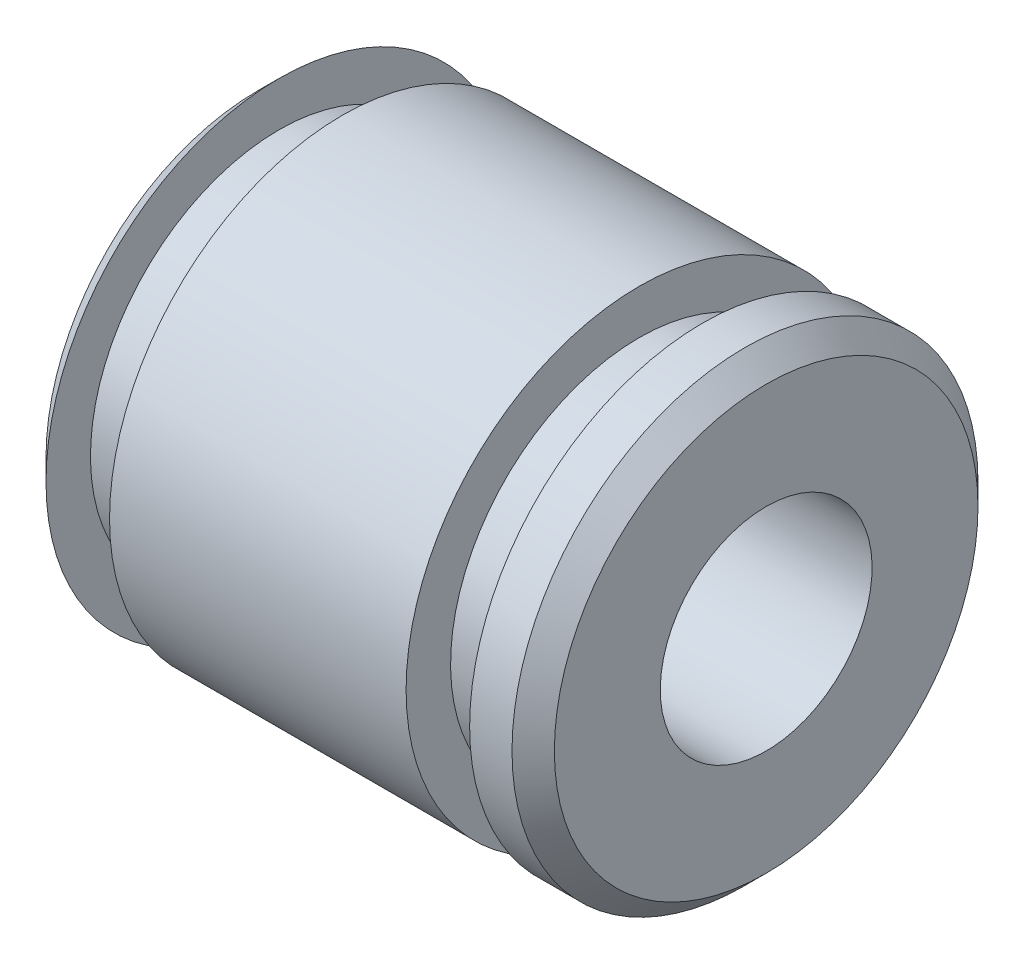
SolidWorks part; units mm, degrees
material "Acciaio al carbonio semplice"
ref_plane "Piano frontale" through (0, 0, 0) normal (0, 0, 1) x (1, 0, 0)
ref_plane "Piano superiore" through (0, 0, 0) normal (0, 1, 0) x (1, 0, 0)
ref_plane "Piano destro" through (0, 0, 0) normal (1, 0, 0) x (0, 0, -1)
sketch "Schizzo1" plane through (0, 0, 0) normal (0, 0, 1) x (1, 0, 0)
  line L0 (0, 0) -> (0, 11)
  line L2 (24, 11) -> (24, 0)
  line L3 (24, 0) -> (0, 0) construction
  line L8 (21, 11) -> (24, 11)
  line L9 (0, 0) -> (24, 0) construction
  line L10 (18, 11) -> (18, 8.9)
  line L11 (18, 8.9) -> (21, 8.9)
  line L12 (21, 8.9) -> (21, 11)
  line L13 (24, 0) -> (0, 0)
  line L15 (1, 8.9) -> (4, 8.9)
  line L16 (4, 8.9) -> (4, 11)
  line L17 (4, 11) -> (18, 11)
  line L18 (0, 11) -> (1, 11)
  line L19 (1, 11) -> (1, 8.9)
  line L20 (0, 0) -> (-4.0571, 0) construction
  dimension "D1" = 2.1
  dimension "D2" = 3
  dimension "D3" = 3
  dimension "D4" = 22
  dimension "D5" = 24
  dimension "D6" = 1
revolve "Rivoluzione1" add sketch "Schizzo1" angle 360 about L3
sketch "Schizzo2" plane through (24, 0, 0) normal (1, 0, 0) x (0, 0, -1)
  circle A0 centre (0, 0) radius 5
  dimension "D1" = 10
extrude "Taglio-Estrusione1" cut sketch "Schizzo2" against normal blind 21
chamfer "Smusso1" distance 1 angle 45 2 edges at (24, 11, 0) (0, 11, 0)
